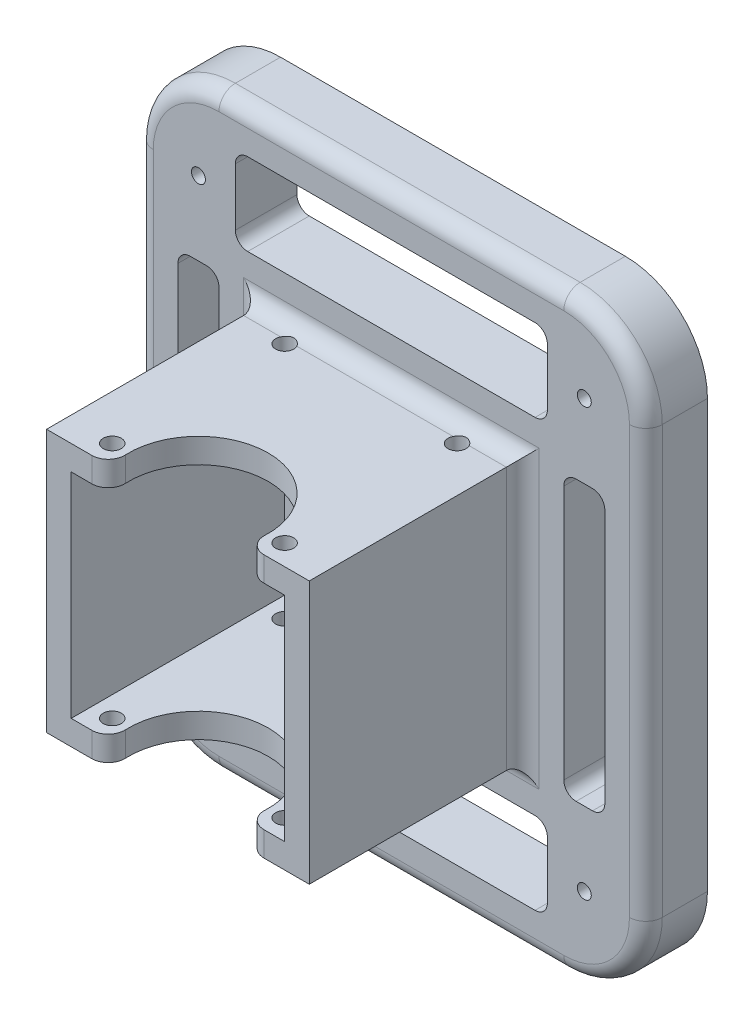
SolidWorks part; units mm, degrees
material "ABS"
ref_plane "正面" through (0, 0, 0) normal (0, 0, 1) x (1, 0, 0)
ref_plane "平面" through (0, 0, 0) normal (0, 1, 0) x (1, 0, 0)
ref_plane "右側面" through (0, 0, 0) normal (1, 0, 0) x (0, 0, -1)
sketch "ｽｹｯﾁ2" plane through (0, 0, 0) normal (0, 0, 1) x (1, 0, 0)
  line L0 (19.8, 0) -> (-19.8, 0) construction
  line L1 (-16, 0) -> (16, 0)
  line L2 (-16, 0) -> (-16, 32)
  line L3 (-16, 32) -> (16, 32)
  line L4 (16, 0) -> (16, 32)
  line L5 (-13, 3) -> (13, 3)
  line L6 (13, 3) -> (13, 29)
  line L7 (-13, 29) -> (13, 29)
  line L8 (-13, 3) -> (-13, 29)
  dimension "D1" = 32
  dimension "D2" = 32
  dimension "D3" = 3
extrude "ﾎﾞｽ - 押し出し1" add sketch "ｽｹｯﾁ2" along normal blind 26
sketch "ｽｹｯﾁ3" plane through (0, 0, 0) normal (0, 0, -1) x (-1, 0, 0)
  line L5 (-16, 0) -> (-16, 32) construction
  line L6 (-31, 52) -> (31, 52)
  line L7 (-31, 52) -> (-31, -20)
  line L8 (-31, -20) -> (31, -20)
  line L9 (31, 52) -> (31, -20)
  line L10 (16, 32) -> (16, 0) construction
  line L11 (-16, 32) -> (16, 32) construction
  line L12 (15.675, 0) -> (-15.675, 0) construction
  dimension "D1" = 15
  dimension "D2" = 15
  dimension "D3" = 20
  dimension "D4" = 20
extrude "ﾎﾞｽ - 押し出し2" add sketch "ｽｹｯﾁ3" along normal blind 7.5
fillet "ﾌｨﾚｯﾄ1" radius 2 4 edges at (0, 0, 0) (16, 16, 0) (-16, 16, 0) (0, 32, 0)
fillet "ﾌｨﾚｯﾄ2" radius 2 4 edges at (-31, 16, 0) (0, 52, 0) (31, 16, 0) (0, -20, 0)
sketch "ｽｹｯﾁ5" plane through (0, 0, 0) normal (0, -1, 0) x (1, 0, 0)
  line L0 (0, 26) -> (0, 0) construction
  line L1 (-16, 26) -> (16, 26) construction
  line L3 (-10.5, 23.5) -> (10.5, 23.5) construction
  line L4 (-10.5, 23.5) -> (-10.5, 2.5) construction
  line L5 (-10.5, 2.5) -> (10.5, 2.5) construction
  line L6 (10.5, 23.5) -> (10.5, 2.5) construction
  line L7 (-10.5, 23.5) -> (10.5, 2.5) construction
  line L8 (-10.5, 2.5) -> (10.5, 23.5) construction
  circle A0 centre (10.5, 23.5) radius 1.1
  circle A1 centre (-10.5, 23.5) radius 1.1
  circle A2 centre (-10.5, 2.5) radius 1.1
  circle A3 centre (10.5, 2.5) radius 1.1
  circle A4 centre (0, 23.5) radius 8.5
  point P5 (0, 13)
  dimension "D4" = 2.2
  dimension "D5" = 17
  dimension "D1" = 21
  dimension "D2" = 21
  dimension "D3" = 13
extrude "ｶｯﾄ - 押し出し1" cut sketch "ｽｹｯﾁ5" against normal through all both and the other way through all
fillet "ﾌｨﾚｯﾄ3" radius 2 4 edges at (-8.124, 30.5, 26) (8.124, 30.5, 26) (-8.124, 1.5, 26) (8.124, 1.5, 26)
sketch "ｽｹｯﾁ7" plane through (0, 0, -7.5) normal (0, 0, -1) x (-1, 0, 0)
  line L1 (-23.5, -10) -> (23.5, -10) construction
  line L2 (-23.5, -10) -> (-23.5, 42) construction
  line L3 (-23.5, 42) -> (23.5, 42) construction
  line L4 (-31, 52) -> (-31, -20)
  line L5 (-31, -20) -> (31, -20)
  line L6 (31, -20) -> (31, 52)
  line L7 (31, 52) -> (-31, 52)
  line L8 (-31, 52) -> (-31, -20) construction
  line L9 (-31, -20) -> (31, -20) construction
  line L10 (31, -20) -> (31, 52) construction
  line L11 (31, 52) -> (-31, 52) construction
  line L12 (23.5, -10) -> (23.5, 42) construction
  circle A0 centre (-23.5, -10) radius 0.85
  circle A1 centre (-23.5, 42) radius 0.85
  circle A2 centre (23.5, 42) radius 0.85
  circle A3 centre (23.5, -10) radius 0.85
  dimension "D6" = 1.7
  dimension "D2" = 10
  dimension "D3" = 10
  dimension "D4" = 7.5
  dimension "D5" = 7.5
  dimension "D1" = 0
extrude "ｶｯﾄ - 押し出し2" cut sketch "ｽｹｯﾁ7" against normal through all
fillet "ﾌｨﾚｯﾄ4" radius 10 8 edges at (-30.4142, 51.4142, -0.5858) (-30.4142, -19.4142, -0.5858) (30.4142, -19.4142, -0.5858) (30.4142, 51.4142, -0.5858) (31, 52, -4.75) (31, -20, -4.75) (-31, -20, -4.75) (-31, 52, -4.75)
sketch "ｽｹｯﾁ8" plane through (0, 0, 0) normal (0, 0, 1) x (1, 0, 0)
  line L0 (21, 50) -> (-21, 50) construction
  line L1 (-17.5, 47) -> (17.5, 47)
  line L2 (-19, 45.5) -> (-19, 38.5)
  line L3 (-17.5, 37) -> (17.5, 37)
  line L4 (19, 45.5) -> (19, 38.5)
  line L5 (22.5, 33) -> (24.5, 33)
  line L6 (21, 31.5) -> (21, 0.5)
  line L7 (22.5, -1) -> (24.5, -1)
  line L8 (26, 31.5) -> (26, 0.5)
  line L9 (-24.5, 33) -> (-22.5, 33)
  line L10 (-26, 31.5) -> (-26, 0.5)
  line L11 (-24.5, -1) -> (-22.5, -1)
  line L12 (-21, 31.5) -> (-21, 0.5)
  line L13 (-17.5, -5) -> (17.5, -5)
  line L14 (-19, -6.5) -> (-19, -13.5)
  line L15 (-17.5, -15) -> (17.5, -15)
  line L16 (19, -6.5) -> (19, -13.5)
  line L17 (-18, 34) -> (18, 34) construction
  line L18 (18, -2) -> (-18, -2) construction
  line L19 (-21, -18) -> (21, -18) construction
  line L20 (-29, 42) -> (-29, -10) construction
  line L21 (29, -10) -> (29, 42) construction
  line L22 (18, 34) -> (18, -2) construction
  line L23 (-18, -2) -> (-18, 34) construction
  arc A0 (-26, 0.5) -> (-24.5, -1) centre (-24.5, 0.5) ccw
  arc A1 (-22.5, 33) -> (-21, 31.5) centre (-22.5, 31.5) cw
  arc A2 (24.5, 33) -> (26, 31.5) centre (24.5, 31.5) cw
  arc A3 (21, 0.5) -> (22.5, -1) centre (22.5, 0.5) ccw
  arc A4 (17.5, -5) -> (19, -6.5) centre (17.5, -6.5) cw
  arc A5 (-19, -13.5) -> (-17.5, -15) centre (-17.5, -13.5) ccw
  arc A6 (17.5, -15) -> (19, -13.5) centre (17.5, -13.5) ccw
  arc A7 (-17.5, -5) -> (-19, -6.5) centre (-17.5, -6.5) ccw
  arc A8 (-22.5, -1) -> (-21, 0.5) centre (-22.5, 0.5) ccw
  arc A9 (-24.5, 33) -> (-26, 31.5) centre (-24.5, 31.5) ccw
  arc A10 (24.5, -1) -> (26, 0.5) centre (24.5, 0.5) ccw
  arc A11 (22.5, 33) -> (21, 31.5) centre (22.5, 31.5) ccw
  arc A12 (17.5, 47) -> (19, 45.5) centre (17.5, 45.5) cw
  arc A13 (-19, 38.5) -> (-17.5, 37) centre (-17.5, 38.5) ccw
  arc A14 (17.5, 37) -> (19, 38.5) centre (17.5, 38.5) ccw
  arc A15 (-17.5, 47) -> (-19, 45.5) centre (-17.5, 45.5) ccw
  dimension "D15" = 1.5
  dimension "D1" = 3
  dimension "D2" = 3
  dimension "D3" = 3
  dimension "D4" = 3
  dimension "D5" = 10
  dimension "D6" = 10
  dimension "D7" = 4
  dimension "D8" = 3
  dimension "D9" = 3
  dimension "D10" = 3
  dimension "D11" = 3
  dimension "D12" = 4
  dimension "D13" = 4
  dimension "D14" = 4
extrude "ｶｯﾄ - 押し出し3" cut sketch "ｽｹｯﾁ8" against normal through all
